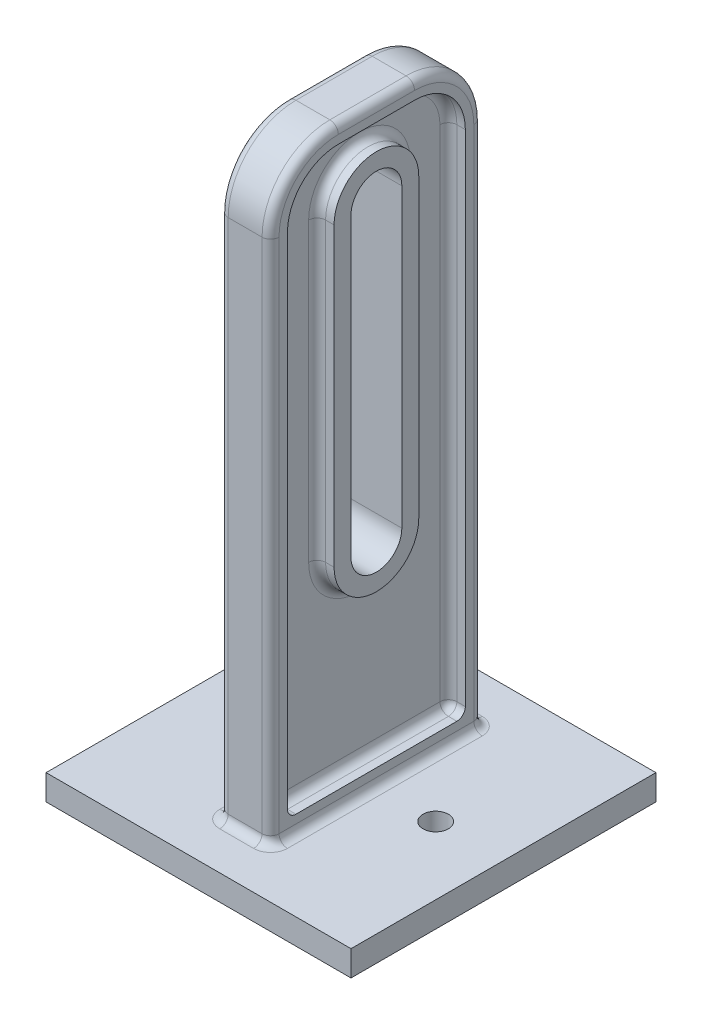
SolidWorks part; units mm, degrees
ref_plane "Front Plane" through (0, 0, 0) normal (0, 0, 1) x (1, 0, 0)
ref_plane "Top Plane" through (0, 0, 0) normal (0, 1, 0) x (1, 0, 0)
ref_plane "Right Plane" through (0, 0, 0) normal (1, 0, 0) x (0, 0, -1)
sketch "Sketch1" plane through (0, 0, 0) normal (0, 1, 0) x (1, 0, 0)
  line L1 (18, -18) -> (-18, -18)
  line L2 (18, -18) -> (18, 18)
  line L3 (18, 18) -> (-18, 18)
  line L4 (-18, -18) -> (-18, 18)
  line L5 (18, -18) -> (-18, 18) construction
  line L6 (18, 18) -> (-18, -18) construction
  point P0 (0, 0)
  dimension "D1" = 36
  dimension "D2" = 36
extrude "Boss-Extrude1" add sketch "Sketch1" along normal blind 3
sketch "Sketch2" plane through (0, 3, 0) normal (0, 1, 0) x (1, 0, 0)
  line L0 (0, 0) -> (-13.7835, 0) construction
  line L1 (0, 0) -> (13.2322, 0) construction
  line L2 (0, 0) -> (0, 14.7024) construction
  circle A0 centre (-10, 0) radius 1.5
  circle A1 centre (10, 0) radius 1.5
  dimension "D1" = 20
  dimension "D2" = 3
extrude "Cut-Extrude1" cut sketch "Sketch2" against normal through all
sketch "Sketch5" plane through (0, 3, 0) normal (0, 1, 0) x (1, 0, 0)
  line L1 (3, -12.5) -> (-3, -12.5)
  line L2 (3, -12.5) -> (3, 12.5)
  line L3 (3, 12.5) -> (-3, 12.5)
  line L4 (-3, -12.5) -> (-3, 12.5)
  line L5 (3, -12.5) -> (-3, 12.5) construction
  line L6 (3, 12.5) -> (-3, -12.5) construction
  point P0 (0, 0)
  dimension "D1" = 25
  dimension "D2" = 6
extrude "Boss-Extrude2" add sketch "Sketch5" along normal blind 70
sketch "Sketch6" plane through (-3, 0, 0) normal (-1, 0, 0) x (0, 0, 1)
  line L0 (-12.5, 73) -> (12.5, 73) construction
  line L5 (-3, 63) -> (-3, 28)
  line L6 (3, 63) -> (3, 28)
  line L7 (0, 63) -> (0, 28) construction
  line L8 (-12.5, 73) -> (-12.5, 3) construction
  line L9 (12.5, 73) -> (12.5, 3) construction
  line L10 (0, 63) -> (-2.0182, 63) construction
  line L11 (0, 28) -> (2.2518, 28) construction
  arc A0 (-3, 63) -> (3, 63) centre (0, 63) cw
  arc A1 (-3, 28) -> (3, 28) centre (0, 28) ccw
  dimension "D2" = 3
  dimension "D3" = 3
  dimension "D1" = 10
  dimension "D4" = 35
extrude "Cut-Extrude3" cut sketch "Sketch6" against normal through all
fillet "Fillet1" radius 8 2 edges at (0, 73, 12.5) (0, 73, -12.5)
sketch "Sketch7" plane through (-3, 0, 0) normal (-1, 0, 0) x (0, 0, 1)
  line L20 (-10.5, 65) -> (-10.5, 5)
  line L21 (-10.5, 5) -> (10.5, 5)
  line L22 (10.5, 5) -> (10.5, 65)
  line L23 (4.5, 71) -> (-4.5, 71)
  line L24 (-10.5, 65) -> (-10.5, 5)
  line L25 (-10.5, 5) -> (10.5, 5)
  line L26 (10.5, 5) -> (10.5, 65)
  line L27 (4.5, 71) -> (-4.5, 71)
  arc A16 (10.5, 65) -> (4.5, 71) centre (4.5, 65) ccw
  arc A17 (-4.5, 71) -> (-10.5, 65) centre (-4.5, 65) ccw
  arc A18 (10.5, 65) -> (4.5, 71) centre (4.5, 65) ccw
  arc A19 (-4.5, 71) -> (-10.5, 65) centre (-4.5, 65) ccw
  dimension "D1" = 2
extrude "Cut-Extrude5" cut sketch "Sketch7" against normal blind 2
sketch "Sketch8" plane through (-1, 0, 0) normal (-1, 0, 0) x (0, 0, 1)
  line L8 (0, 63) -> (0, 28) construction
  line L10 (5, 28) -> (5, 63)
  line L11 (-5, 63) -> (-5, 28)
  line L12 (5, 28) -> (5, 63)
  line L13 (-5, 63) -> (-5, 28)
  line L14 (3, 63) -> (3, 28)
  line L15 (-3, 63) -> (-3, 28)
  arc A6 (3, 63) -> (-3, 63) centre (0, 63) ccw
  arc A8 (-5, 28) -> (5, 28) centre (0, 28) ccw
  arc A9 (5, 63) -> (-5, 63) centre (0, 63) ccw
  arc A10 (-5, 28) -> (5, 28) centre (0, 28) ccw
  arc A11 (5, 63) -> (-5, 63) centre (0, 63) ccw
  arc A13 (-3, 28) -> (3, 28) centre (0, 28) ccw
  point P0 (0, 45.5)
  dimension "D2" = 3
  dimension "D1" = 2
extrude "Boss-Extrude4" add sketch "Sketch8" along normal blind 2
mirror "Mirror1" about plane through (0, 0, 0) normal (1, 0, 0) of "Cut-Extrude5", "Boss-Extrude4"
fillet "Fillet2" radius 1 34 edges at (-1, 23, 0) (-1, 45.5, -5) (-1, 68, 0) (-1, 45.5, 5) (0, 3, -12.5) (-3, 3, 0) (-1, 5, 0) (-3, 35, 10.5) (-3, 69.2426, 8.7426) (-3, 71, 0) (-3, 69.2426, -8.7426) (-3, 35, -10.5) (-3, 34, -12.5) (-3, 70.6569, -10.1569) (-3, 73, 0) (-3, 70.6569, 10.1569) (-3, 34, 12.5) (0, 3, 12.5) (3, 3, 0) (3, 34, 12.5) (3, 70.6569, 10.1569) (3, 73, 0) (3, 70.6569, -10.1569) (3, 34, -12.5) (1, 45.5, 5) (1, 23, 0) (1, 68, 0) (1, 45.5, -5) (1, 69.2426, 8.7426) (1, 71, 0) (1, 69.2426, -8.7426) (1, 35, 10.5) (1, 5, 0) (1, 35, -10.5)
fillet "Fillet3" radius 1 13 edges at (-1, 35.5, 10.5) (-1, 69.2426, 8.7426) (-1, 71, 0) (-1, 69.2426, -8.7426) (-1, 35.5, -10.5) (1.2929, 5.2929, 10.2071) (2.5, 5, 10.5) (1.2929, 5.2929, -10.2071) (2.5, 5, -10.5) (-2.7071, 5, 10.7929) (-1.2929, 5.2929, 10.5) (-1.2929, 5.2929, -10.5) (-2.7071, 5, -10.7929)
